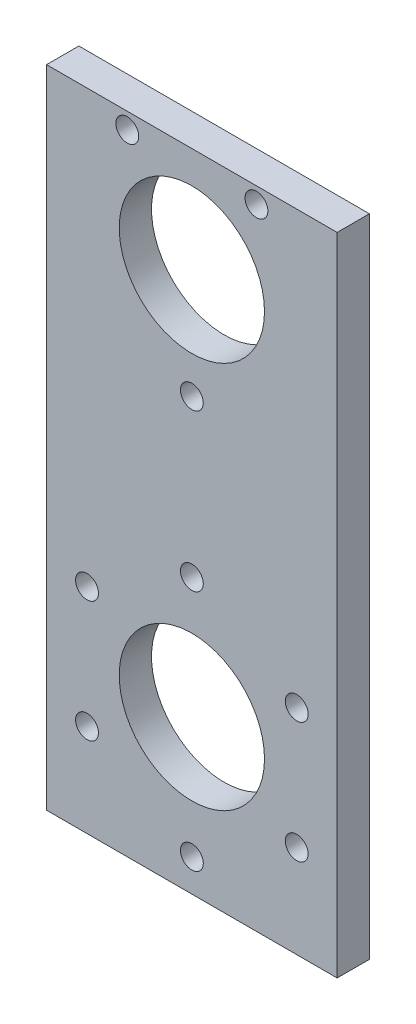
SolidWorks part; units mm, degrees
material "6061-T6 (SS)"
ref_plane "Front Plane" through (0, 0, 0) normal (0, 0, 1) x (1, 0, 0)
ref_plane "Top Plane" through (0, 0, 0) normal (0, 1, 0) x (1, 0, 0)
ref_plane "Right Plane" through (0, 0, 0) normal (1, 0, 0) x (0, 0, -1)
sketch "Sketch1" plane through (0, 0, 0) normal (0, 0, 1) x (1, 0, 0)
  line L0 (0, -38.1) -> (0, 38.1) construction
  line L2 (-28.575, 68.2625) -> (28.575, 68.2625)
  line L3 (-28.575, 68.2625) -> (-28.575, -68.2625)
  line L4 (-28.575, -68.2625) -> (28.575, -68.2625)
  line L5 (28.575, 68.2625) -> (28.575, -68.2625)
  line L6 (-28.575, 68.2625) -> (28.575, -68.2625) construction
  line L7 (-28.575, -68.2625) -> (28.575, 68.2625) construction
  circle A0 centre (0, 38.1) radius 14.2875
  circle A1 centre (0, -38.1) radius 14.2875
  point P7 (0, 0)
  point P18 (0, -38.1)
  dimension "D1" = 28.575
  dimension "D2" = 76.2
  dimension "D6" = 136.525
  dimension "D7" = 57.15
extrude "Boss-Extrude1" add sketch "Sketch1" along normal mid plane 6.35
hole_wizard "#8 Clearance Hole1" positions "Sketch3" profile "Sketch2" hole size "#8" standard "ANSI Inch" end condition through all
sketch "Sketch3" plane through (0, 0, 3.175) normal (0, 0, 1) x (1, 0, 0)
  circle A0 centre (0, -38.1) radius 14.2875 construction
  point P0 (0, -14.2875)
  point P10 (20.6222, -26.1937)
  point P11 (20.6222, -50.0062)
  point P12 (0, -61.9125)
  point P13 (-20.6222, -50.0063)
  point P14 (-20.6222, -26.1938)
  point P15 (0, -38.1)
  dimension "D1" = 23.8125
  dimension "D2" = 6
sketch "Sketch2" plane through (0, -14.2875, 3.175) normal (1, 0, 0) x (0, -1, 0)
  line L0 (0, 0) -> (0, 6.35)
  line L1 (0, 6.35) -> (2.2479, 6.35)
  line L2 (2.2479, 6.35) -> (2.2479, 0)
  line L5 (2.2479, 0) -> (0, 0)
  line L11 (0, -6.35) -> (0, 107.95) construction
  dimension "Thru Hole Dia." = 4.4958
  dimension "Thru Hole Depth" = 6.35
hole_wizard "#8 Clearance Hole2" positions "Sketch7" profile "Sketch5" hole size "#8" standard "ANSI Inch" end condition through all
sketch "Sketch7" plane through (0, 0, 3.175) normal (0, 0, 1) x (1, 0, 0)
  line L0 (-12.7, 55.5625) -> (12.7, 55.5625) construction
  line L2 (28.575, 68.2625) -> (-28.575, 68.2625) construction
  circle A3 centre (0, 38.1) radius 15.875
  circle A4 centre (0, 38.1) radius 15.875 construction
  circle A5 centre (-12.7, 55.5625) radius 7.9375 construction
  circle A8 centre (0, 16.51) radius 7.9375 construction
  point P0 (-12.7, 55.5625)
  point P2 (12.7, 55.5625)
  point P9 (0, 55.5625)
  point P29 (0, 16.51)
  dimension "D4" = 15.875
  dimension "D1" = 25.4
  dimension "D2" = 12.7
  dimension "D5" = 21.59
  dimension "D3" = 1.5875
sketch "Sketch5" plane through (-12.7, 55.5625, 3.175) normal (1, 0, 0) x (0, -1, 0)
  line L0 (0, 0) -> (0, 6.35)
  line L1 (0, 6.35) -> (2.2479, 6.35)
  line L2 (2.2479, 6.35) -> (2.2479, 0)
  line L5 (2.2479, 0) -> (0, 0)
  line L11 (0, -6.35) -> (0, 107.95) construction
  dimension "Thru Hole Dia." = 4.4958
  dimension "Thru Hole Depth" = 6.35
sketch "Sketch9" plane through (0, 0, 3.175) normal (0, 0, 1) x (1, 0, 0)
  line L0 (28.575, -68.2625) -> (28.575, 68.2625) construction
  line L1 (-28.575, 58.7375) -> (28.575, 58.7375)
  line L3 (-28.575, -68.2625) -> (28.575, -68.2625)
  line L7 (-28.575, 68.2625) -> (28.575, 68.2625)
  line L8 (-28.575, 68.2625) -> (-28.575, 58.7375)
  line L10 (28.575, 68.2625) -> (28.575, 58.7375)
  circle A0 centre (0, -61.9125) radius 2.2479 construction
  line M11 (28.575, -68.2625) -> (28.575, 68.2625)
  line M12 (28.575, 68.2625) -> (-28.575, 68.2625)
  line M13 (-28.575, 68.2625) -> (-28.575, -68.2625)
  dimension "D1" = 127
  dimension "D2" = 57.15
  dimension "D3" = 6.35
extrude "Cut-Extrude1" cut sketch "Sketch9" against normal through all contours L1 M13 M11 M12 region at (0, 63.5, 3.175)
